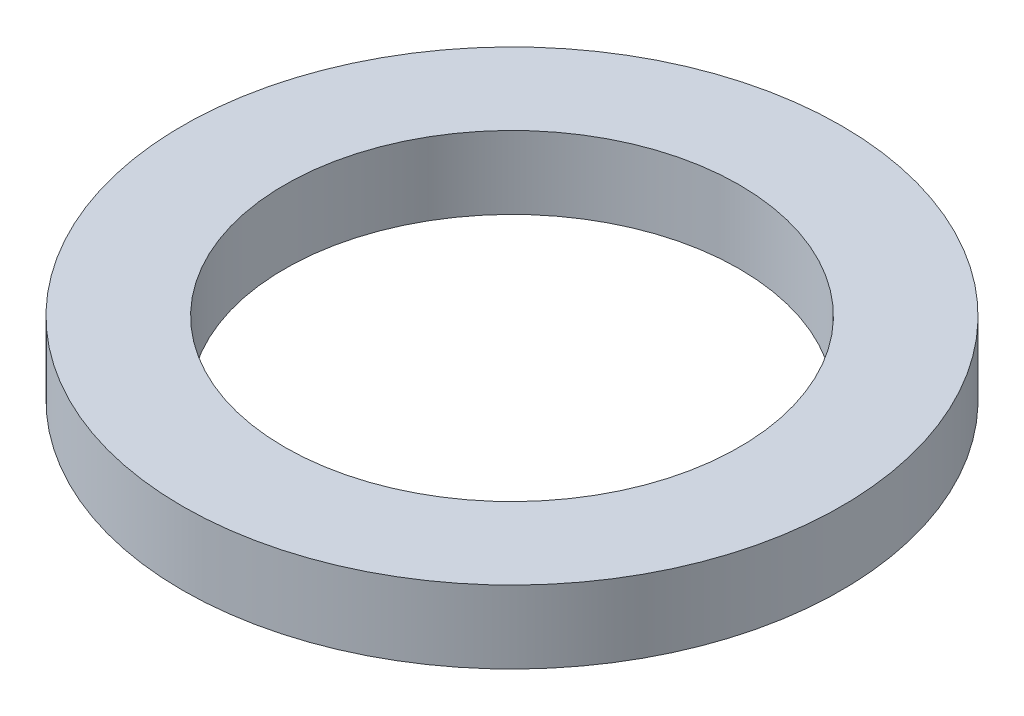
SolidWorks part; units mm, degrees
ref_plane "Front Plane" through (0, 0, 0) normal (0, 0, 1) x (1, 0, 0)
ref_plane "Top Plane" through (0, 0, 0) normal (0, 1, 0) x (1, 0, 0)
ref_plane "Right Plane" through (0, 0, 0) normal (1, 0, 0) x (0, 0, -1)
sketch "Sketch1" plane through (0, 0, 0) normal (0, 1, 0) x (1, 0, 0)
  circle A0 centre (0, 0) radius 72.5
  dimension "FLANGE_OD" = 145
extrude "Boss-Extrude1" add sketch "Sketch1" along normal blind 16
sketch "Sketch2" plane through (0, 0, 0) normal (0, 1, 0) x (1, 0, 0)
  circle A0 centre (0, 0) radius 50
  dimension "BORE_D" = 100
extrude "Cut-Extrude1" cut sketch "Sketch2" along normal through all
sketch "Sketch3" plane through (0, 16, 0) normal (0, 1, 0) x (1, 0, 0)
  circle A0 centre (0, 0) radius 27.2621 construction
  circle A1 centre (-27.2621, 0) radius 3.1411
  dimension "BOLT_D" = 6.2823
  dimension "BOLT_PCD" = 54.5243
extrude "Cut-Extrude2" cut sketch "Sketch3" against normal blind 13.4538 rebuild error yes
pattern_circular "CirPattern1" count 5 over 360 rebuild error yes
